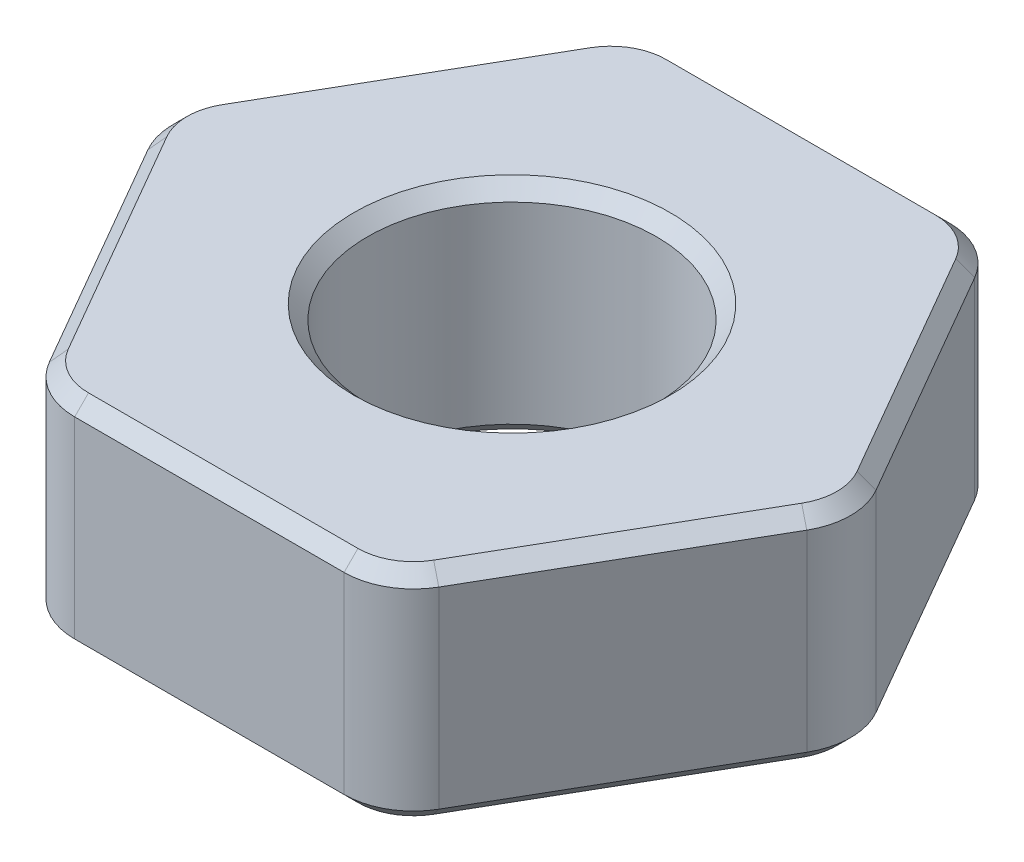
SolidWorks part; units mm, degrees
ref_plane "Front" through (0, 0, 0) normal (0, 0, 1) x (1, 0, 0)
ref_plane "Top" through (0, 0, 0) normal (0, 1, 0) x (1, 0, 0)
ref_plane "Right" through (0, 0, 0) normal (1, 0, 0) x (0, 0, -1)
sketch "Sketch1" plane through (0, 0, 0) normal (0, 1, 0) x (1, 0, 0)
  line L1 (2.5205, 4.3656) -> (-2.5205, 4.3656)
  line L2 (-2.5205, 4.3656) -> (-5.041, 0)
  line L3 (-5.041, 0) -> (-2.5205, -4.3656)
  line L4 (-2.5205, -4.3656) -> (2.5205, -4.3656)
  line L5 (2.5205, -4.3656) -> (5.041, 0)
  line L6 (5.041, 0) -> (2.5205, 4.3656)
  circle A0 centre (0, 0) radius 4.3656 construction
  circle A1 centre (0, 0) radius 2.0828
  dimension "D2" = 4.1656
  dimension "D1" = 8.7312
extrude "Boss-Extrude1" add sketch "Sketch1" along normal mid plane 3.175
fillet "Fillet1" radius 1 6 edges at (5.041, 0, 0) (2.5205, 0, 4.3656) (-5.041, 0, 0) (-2.5205, 0, -4.3656) (2.5205, 0, -4.3656) (-2.5205, 0, 4.3656)
chamfer "Chamfer1" distance 0.2 angle 45 26 edges at (0, -1.5875, 2.0828) (2.4431, -1.5875, -4.2317) (0, -1.5875, -4.3656) (-2.4431, -1.5875, -4.2317) (-3.7807, -1.5875, -2.1828) (-4.8863, -1.5875, 0) (-3.7807, -1.5875, 2.1828) (-2.4431, -1.5875, 4.2317) (0, -1.5875, 4.3656) (2.4431, -1.5875, 4.2317) (3.7807, -1.5875, 2.1828) (4.8863, -1.5875, 0) (3.7807, -1.5875, -2.1828) (0, 1.5875, 2.0828) (2.4431, 1.5875, 4.2317) (0, 1.5875, 4.3656) (-2.4431, 1.5875, 4.2317) (-3.7807, 1.5875, 2.1828) (-4.8863, 1.5875, 0) (-3.7807, 1.5875, -2.1828) (-2.4431, 1.5875, -4.2317) (0, 1.5875, -4.3656) (2.4431, 1.5875, -4.2317) (3.7807, 1.5875, -2.1828) (4.8863, 1.5875, 0) (3.7807, 1.5875, 2.1828)
